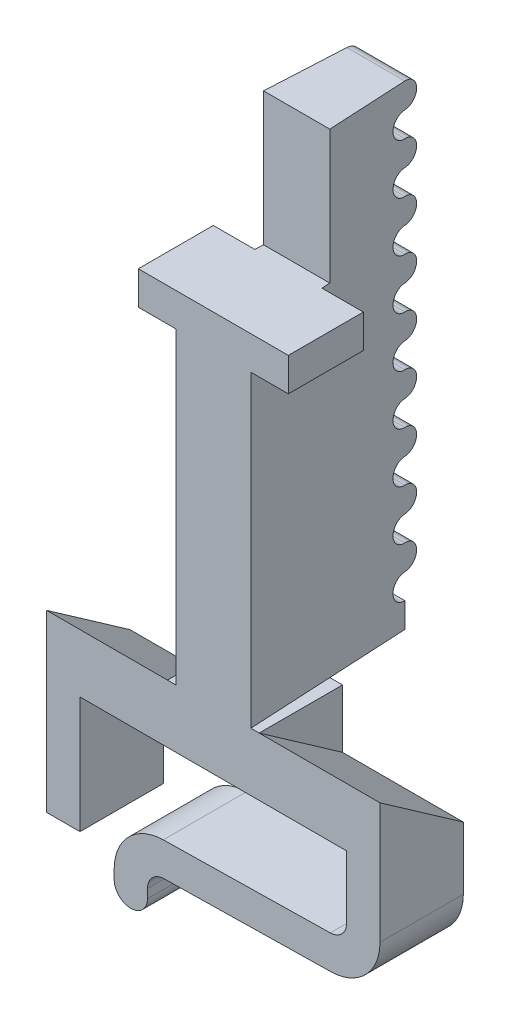
SolidWorks part; units mm, degrees
ref_plane "Front" through (0, 0, 0) normal (0, 0, 1) x (1, 0, 0)
ref_plane "Top" through (0, 0, 0) normal (0, 1, 0) x (1, 0, 0)
ref_plane "Right" through (0, 0, 0) normal (1, 0, 0) x (0, 0, -1)
sketch "Model" plane through (0, 0, 0) normal (0, 0, 1) x (1, 0, 0)
  line L0 (2.794, 15.748) -> (7.366, 15.748)
  line L1 (9.144, 3.556) -> (9.144, 1.6508)
  line L2 (8.6449, 1.1428) -> (3.5548, 1.054)
  line L3 (8.6626, 0.127) -> (3.5725, 0.0382)
  line L4 (2.0574, -0.4698) -> (2.0574, -0.7416)
  line L5 (3.0734, -0.4698) -> (3.0734, -0.7416)
  line L58 (0, 0) -> (1.016, 0)
  line L61 (1.016, 3.556) -> (9.144, 3.556)
  line L62 (0, 5.334) -> (0, 0)
  line L63 (1.016, 0) -> (1.016, 3.556)
  line L64 (10.16, 5.334) -> (6.223, 5.334)
  line L65 (0, 5.334) -> (3.937, 5.334)
  line L67 (2.794, 15.748) -> (2.794, 14.732)
  line L69 (3.937, 14.732) -> (3.937, 5.334)
  line L72 (6.223, 14.732) -> (6.223, 5.334)
  line L73 (7.366, 15.748) -> (7.366, 14.732)
  line L75 (10.16, 1.6508) -> (10.16, 5.334)
  line L76 (2.794, 14.732) -> (3.937, 14.732)
  line L77 (6.223, 14.732) -> (7.366, 14.732)
  arc A0 (10.16, 1.6508) -> (8.6626, 0.127) centre (8.636, 1.6508) cw
  arc A1 (9.144, 1.6508) -> (8.6449, 1.1428) centre (8.636, 1.6508) cw
  arc A2 (3.5725, 0.0382) -> (3.0734, -0.4698) centre (3.5814, -0.4698) ccw
  arc A3 (3.5548, 1.054) -> (2.0574, -0.4698) centre (3.5814, -0.4698) ccw
  arc A4 (2.0574, -0.7416) -> (3.0734, -0.7416) centre (2.5654, -0.7416) ccw
  point P5 (5.08, 15.748)
  point P8 (5.08, 3.556)
  point P18 (2.5654, -1.2496)
  dimension "D2" = 10.16
  dimension "D18" = 0.508
  dimension "D14" = 0.508
  dimension "D16" = 0.508
  dimension "D4" = 10.414
  dimension "D5" = 1.016
  dimension "D7" = 2.286
  dimension "D8" = 1.778
  dimension "D10" = 5.334
  dimension "D11" = 1.016
  dimension "D12" = 4.572
  dimension "D13" = 1.016
  dimension "D15" = 91
  dimension "D17" = 5.207
  dimension "D20" = 2.286
  dimension "D21" = 1.5494
extrude "Boss-Extrude1" add sketch "Model" against normal blind 2.54
sketch "Sketch1" plane through (0, 0, 0) normal (1, 0, 0) x (0, 0, -1)
  line L0 (0, 5.334) -> (2.54, 5.334)
  line L1 (2.54, 5.334) -> (2.54, 3.5555)
  line L2 (2.54, 3.5555) -> (0, 5.334)
  line L3 (2.54, 1.6508) -> (2.54, 5.334) construction
  dimension "D1" = 35
extrude "Cut-Extrude2" cut sketch "Sketch1" along normal blind 3.683
extrude "Cut-Extrude4" cut sketch "Sketch1<3>" against normal blind 3.683 from surface starting at face at (10.16, 3.4924, -1.27)
sketch "Sketch1<3>" plane through (0, 0, 0) normal (1, 0, 0) x (0, 0, -1) same geometry as "Sketch1"
sketch "Sketch2" plane through (0, 0, -2.54) normal (0, 0, -1) x (-1, 0, 0)
  line L1 (-6.223, 5.334) -> (-3.937, 5.334)
  line L2 (-6.223, 5.334) -> (-6.223, 19.812)
  line L3 (-6.223, 19.812) -> (-3.937, 19.812)
  line L4 (-3.937, 5.334) -> (-3.937, 19.812)
  line L5 (-3.937, 14.732) -> (-3.937, 5.334) construction
  line L6 (-6.223, 5.334) -> (-6.223, 14.732) construction
  dimension "D1" = 14.478
extrude "Boss-Extrude2" add sketch "Sketch2" along normal blind 2.794
sketch "Sketch3" plane through (0, 0, -2.54) normal (0, 0, -1) x (-1, 0, 0)
  line L1 (-6.223, 15.748) -> (-7.366, 15.748)
  line L2 (-6.223, 15.748) -> (-6.223, 14.732)
  line L3 (-6.223, 14.732) -> (-7.366, 14.732)
  line L4 (-7.366, 15.748) -> (-7.366, 14.732)
  line L5 (-2.794, 15.748) -> (-3.937, 15.748)
  line L6 (-2.794, 15.748) -> (-2.794, 14.732)
  line L7 (-2.794, 14.732) -> (-3.937, 14.732)
  line L8 (-3.937, 15.748) -> (-3.937, 14.732)
extrude "Cut-Extrude5" cut sketch "Sketch3" against normal blind 0.254
draft "Draft2" type of draft neutral plane draft angle 3 faces to draft 2 face at (6.223, 12.954, -2.667) face at (3.937, 12.7282, -2.667) neutral plane through (8.636, 1.6508, 0) neutral plane normal (0, 0, 1) reverse direction yes parameters "D1"=3
sketch "Sketch4" plane through (0, 0, 0) normal (1, 0, 0) x (0, 0, -1)
  line L0 (5.334, 19.812) -> (2.54, 19.812) construction
  line L1 (5.334, 19.812) -> (5.334, 5.334) construction
  line L3 (4.953, 6.096) -> (4.953, 3.556)
  line L6 (5.334, 3.556) -> (2.54, 3.556) construction
  line L7 (4.953, 3.556) -> (5.334, 3.556)
  line L8 (5.334, 3.556) -> (5.334, 19.812)
  line L9 (5.334, 19.812) -> (4.953, 19.812)
  arc A0 (4.953, 19.812) -> (5.334, 19.431) centre (4.953, 19.431) cw
  arc A1 (5.334, 19.431) -> (4.953, 19.05) centre (4.953, 19.431) cw
  arc A2 (4.953, 19.05) -> (4.572, 18.669) centre (4.953, 18.669) ccw
  arc A3 (4.572, 18.669) -> (4.953, 18.288) centre (4.953, 18.669) ccw
  arc A4 (4.953, 18.288) -> (5.334, 17.907) centre (4.953, 17.907) cw
  arc A5 (5.334, 17.907) -> (4.953, 17.526) centre (4.953, 17.907) cw
  arc A6 (4.953, 17.526) -> (4.572, 17.145) centre (4.953, 17.145) ccw
  arc A7 (4.572, 17.145) -> (4.953, 16.764) centre (4.953, 17.145) ccw
  arc A8 (4.953, 16.764) -> (5.334, 16.383) centre (4.953, 16.383) cw
  arc A9 (5.334, 16.383) -> (4.953, 16.002) centre (4.953, 16.383) cw
  arc A10 (4.953, 16.002) -> (4.572, 15.621) centre (4.953, 15.621) ccw
  arc A11 (4.572, 15.621) -> (4.953, 15.24) centre (4.953, 15.621) ccw
  arc A12 (4.953, 15.24) -> (5.334, 14.859) centre (4.953, 14.859) cw
  arc A13 (5.334, 14.859) -> (4.953, 14.478) centre (4.953, 14.859) cw
  arc A14 (4.953, 14.478) -> (4.572, 14.097) centre (4.953, 14.097) ccw
  arc A15 (4.572, 14.097) -> (4.953, 13.716) centre (4.953, 14.097) ccw
  arc A16 (4.953, 13.716) -> (5.334, 13.335) centre (4.953, 13.335) cw
  arc A17 (5.334, 13.335) -> (4.953, 12.954) centre (4.953, 13.335) cw
  arc A18 (4.953, 12.954) -> (4.572, 12.573) centre (4.953, 12.573) ccw
  arc A19 (4.572, 12.573) -> (4.953, 12.192) centre (4.953, 12.573) ccw
  arc A20 (4.953, 12.192) -> (5.334, 11.811) centre (4.953, 11.811) cw
  arc A21 (5.334, 11.811) -> (4.953, 11.43) centre (4.953, 11.811) cw
  arc A22 (4.953, 11.43) -> (4.572, 11.049) centre (4.953, 11.049) ccw
  arc A23 (4.572, 11.049) -> (4.953, 10.668) centre (4.953, 11.049) ccw
  arc A24 (4.953, 10.668) -> (5.334, 10.287) centre (4.953, 10.287) cw
  arc A25 (5.334, 10.287) -> (4.953, 9.906) centre (4.953, 10.287) cw
  arc A26 (4.953, 9.906) -> (4.572, 9.525) centre (4.953, 9.525) ccw
  arc A27 (4.572, 9.525) -> (4.953, 9.144) centre (4.953, 9.525) ccw
  arc A28 (4.953, 9.144) -> (5.334, 8.763) centre (4.953, 8.763) cw
  arc A29 (5.334, 8.763) -> (4.953, 8.382) centre (4.953, 8.763) cw
  arc A30 (4.953, 8.382) -> (4.572, 8.001) centre (4.953, 8.001) ccw
  arc A31 (4.572, 8.001) -> (4.953, 7.62) centre (4.953, 8.001) ccw
  arc A32 (4.953, 7.62) -> (5.334, 7.239) centre (4.953, 7.239) cw
  arc A33 (5.334, 7.239) -> (4.953, 6.858) centre (4.953, 7.239) cw
  arc A34 (4.953, 6.858) -> (4.572, 6.477) centre (4.953, 6.477) ccw
  arc A35 (4.572, 6.477) -> (4.953, 6.096) centre (4.953, 6.477) ccw
  dimension "D1" = 0.381
  dimension "D2" = 0.381
  dimension "D3" = 0.381
  dimension "D4" = 0.381
  dimension "D5" = 9
extrude "Cut-Extrude6" cut sketch "Sketch4" along normal through all contours L9 A0 L8 | A3 A4 L8 A1 A2 | A7 A8 L8 A5 A6 | A11 A12 L8 A9 A10 | A15 A16 L8 A13 A14 | A19 A20 L8 A17 A18 | A23 A24 L8 A21 A22 | A27 A28 L8 A25 A26 | A31 A32 L8 A29 A30 | A34 A35 L3 L7 L8 A33 region at (0, 5.4335, -5.0927) region at (0, 19.7269, -5.2489) region at (0, 18.669, -5.0165) region at (0, 17.145, -5.0165) region at (0, 15.621, -5.0165) region at (0, 14.097, -5.0165) region at (0, 12.573, -5.0165) region at (0, 11.049, -5.0165) region at (0, 9.525, -5.0165) region at (0, 8.001, -5.0165)
